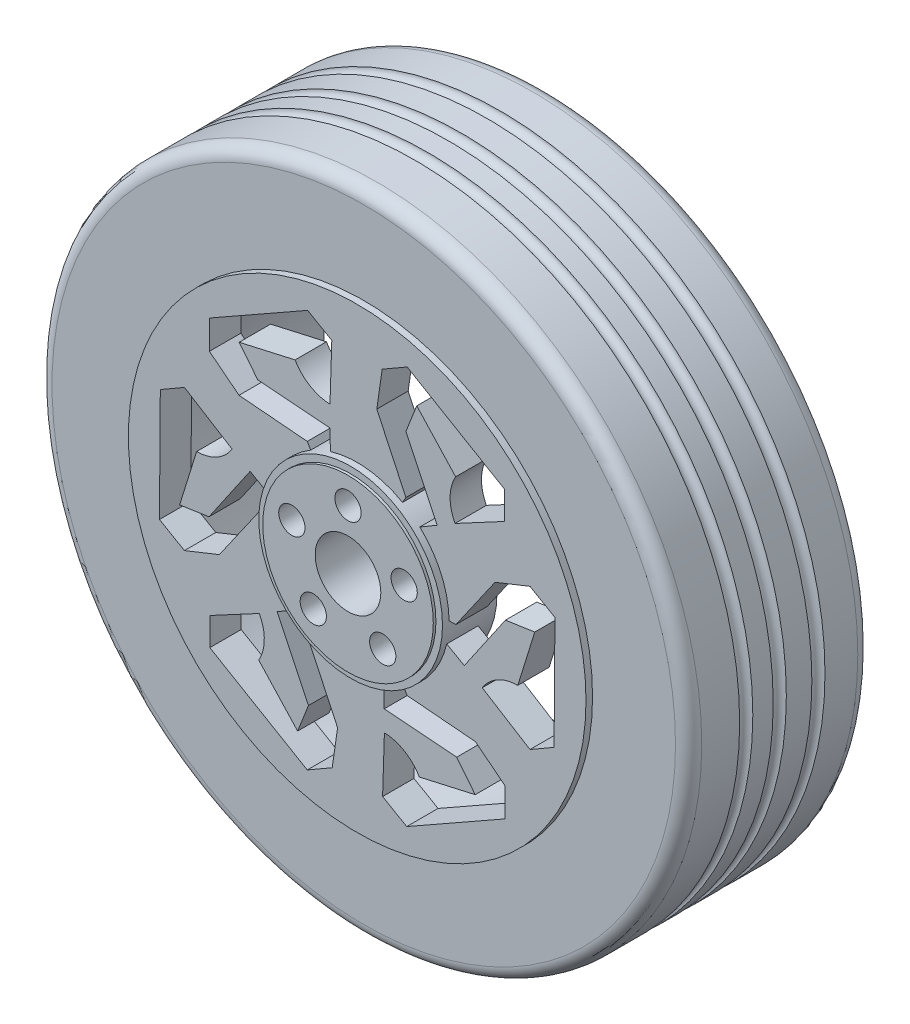
SolidWorks part; units mm, degrees
ref_plane "Front Plane" through (0, 0, 0) normal (0, 0, 1) x (1, 0, 0)
ref_plane "Top Plane" through (0, 0, 0) normal (0, 1, 0) x (1, 0, 0)
ref_plane "Right Plane" through (0, 0, 0) normal (1, 0, 0) x (0, 0, -1)
sketch "Sketch2" plane through (0, 0, 0) normal (0, 0, 1) x (1, 0, 0)
  circle A0 centre (0, 0) radius 247.55
  dimension "D1" = 495.1
extrude "Boss-Extrude1" add sketch "Sketch2" along normal blind 138.9
sketch "Sketch3" plane through (0, 0, 138.9) normal (0, 0, 1) x (1, 0, 0)
  circle A0 centre (0, 0) radius 174.35
  dimension "D1" = 348.7
fillet "Fillet1" radius 10 1 edges at (247.55, 0, 138.9)
fillet "Fillet2" radius 10 1 edges at (247.55, 0, 0)
extrude "Boss-Extrude2" add sketch "Sketch3" along normal blind 5
sketch "Sketch5" plane through (0, 0, 143.9) normal (0, 0, 1) x (1, 0, 0)
  line L0 (105.0037, 43.3694) -> (131.6337, 54.0214)
  line L1 (131.6337, 54.0214) -> (150.6653, 43.0319)
  line L2 (150.6653, 43.0319) -> (150.3446, -0.3609)
  line L3 (150.3446, -0.3609) -> (150.0291, -43.0412)
  line L4 (150.0291, -43.0412) -> (131.6404, -53.6579)
  line L5 (131.6404, -53.6579) -> (95.2902, -31.0843)
  line L7 (122.3632, -15.976) -> (135.2996, 25.6977)
  line L8 (135.2996, 25.6977) -> (112.9256, 22.3447)
  line L10 (112.9256, 22.3447) -> (81.5922, -23.3101)
  line L11 (81.5922, -23.3101) -> (40.2577, 0.1488)
  line L12 (40.2577, 0.1488) -> (75.1777, 0.5509)
  line L13 (75.1777, 0.5509) -> (105.0037, 43.3694)
  line L14 (90.0609, -69.2512) -> (112.6007, -86.9874)
  line L16 (112.6007, -86.9874) -> (112.5994, -108.964)
  line L17 (112.5994, -108.964) -> (74.8597, -130.3827)
  line L18 (74.8597, -130.3827) -> (37.7398, -151.4496)
  line L19 (37.7398, -151.4496) -> (19.3511, -140.8329)
  line L20 (19.3511, -140.8329) -> (20.7253, -98.0659)
  line L21 (47.346, -113.9577) -> (89.9046, -104.3241)
  line L22 (89.9046, -104.3241) -> (75.8138, -86.6241)
  line L23 (19.0329, 141.0088) -> (38.0659, 151.9959)
  line L24 (38.0659, 151.9959) -> (75.4849, 130.0217)
  line L25 (75.4849, 130.0217) -> (112.2893, 108.4084)
  line L26 (112.2893, 108.4084) -> (112.2893, 87.175)
  line L27 (112.2893, 87.175) -> (74.5649, 66.9816)
  line L28 (75.0173, 97.9817) -> (45.395, 130.0217)
  line L29 (45.395, 130.0217) -> (37.1117, 108.9688)
  line L30 (37.1117, 108.9688) -> (60.9833, 59.0059)
  line L31 (60.9833, 59.0059) -> (20, 34.9386)
  line L32 (20, 34.9386) -> (37.1117, 65.3813)
  line L33 (37.1117, 65.3813) -> (14.9428, 112.6206)
  line L34 (14.9428, 112.6206) -> (19.0329, 141.0088)
  line L35 (75.8138, -86.6241) -> (20.6089, -82.316)
  line L36 (20.6089, -82.316) -> (20.2577, -34.7898)
  line L37 (20.2577, -34.7898) -> (38.066, -64.8303)
  line L38 (38.066, -64.8303) -> (90.0609, -69.2512)
  line L39 (-14.9428, -112.6206) -> (-19.0329, -141.0088)
  line L40 (-19.0329, -141.0088) -> (-38.0659, -151.9959)
  line L41 (-38.0659, -151.9959) -> (-75.4849, -130.0217)
  line L42 (-75.4849, -130.0217) -> (-112.2893, -108.4084)
  line L43 (-112.2893, -108.4084) -> (-112.2893, -87.175)
  line L44 (-112.2893, -87.175) -> (-74.5649, -66.9816)
  line L45 (-75.0173, -97.9817) -> (-45.395, -130.0217)
  line L46 (-45.395, -130.0217) -> (-37.1117, -108.9687)
  line L47 (-37.1117, -108.9687) -> (-60.9833, -59.0059)
  line L48 (-60.9833, -59.0059) -> (-20, -34.9386)
  line L49 (-20, -34.9386) -> (-37.1117, -65.3812)
  line L50 (-37.1117, -65.3812) -> (-14.9428, -112.6206)
  line L51 (-105.0037, -43.3694) -> (-131.6337, -54.0214)
  line L52 (-131.6337, -54.0214) -> (-150.6653, -43.0319)
  line L53 (-150.6653, -43.0319) -> (-150.3446, 0.3609)
  line L54 (-150.3446, 0.3609) -> (-150.0291, 43.0412)
  line L55 (-150.0291, 43.0412) -> (-131.6404, 53.6579)
  line L56 (-131.6404, 53.6579) -> (-95.2902, 31.0843)
  line L57 (-122.3632, 15.976) -> (-135.2996, -25.6977)
  line L58 (-135.2996, -25.6977) -> (-112.9256, -22.3447)
  line L59 (-112.9256, -22.3447) -> (-81.5922, 23.3101)
  line L60 (-81.5922, 23.3101) -> (-40.2577, -0.1488)
  line L61 (-40.2577, -0.1488) -> (-75.1777, -0.5509)
  line L62 (-75.1777, -0.5509) -> (-105.0037, -43.3694)
  line L63 (-90.0609, 69.2512) -> (-112.6007, 86.9874)
  line L64 (-112.6007, 86.9874) -> (-112.5994, 108.964)
  line L65 (-112.5994, 108.964) -> (-74.8597, 130.3827)
  line L66 (-74.8597, 130.3827) -> (-37.7398, 151.4496)
  line L67 (-37.7398, 151.4496) -> (-19.3511, 140.8329)
  line L68 (-19.3511, 140.8329) -> (-20.7253, 98.0659)
  line L69 (-47.346, 113.9577) -> (-89.9046, 104.3241)
  line L70 (-89.9046, 104.3241) -> (-75.8138, 86.6241)
  line L71 (-75.8138, 86.6241) -> (-20.6089, 82.316)
  line L72 (-20.6089, 82.316) -> (-20.2577, 34.7898)
  line L73 (-20.2577, 34.7898) -> (-38.066, 64.8303)
  line L74 (-38.066, 64.8303) -> (-90.0609, 69.2512)
  arc A2 (74.5649, 66.9816) -> (75.0173, 97.9817) centre (102.7589, 82.0735) cw
  arc A3 (95.2902, -31.0843) -> (122.3632, -15.976) centre (122.4571, -47.955) cw
  arc A4 (20.7253, -98.0659) -> (47.346, -113.9577) centre (19.6983, -130.0285) cw
  arc A5 (-74.5649, -66.9816) -> (-75.0173, -97.9817) centre (-102.7589, -82.0735) cw
  arc A6 (-95.2902, 31.0843) -> (-122.3632, 15.976) centre (-122.4571, 47.955) cw
  arc A7 (-20.7253, 98.0659) -> (-47.346, 113.9577) centre (-19.6983, 130.0285) cw
  point P87 (0, 0)
  dimension "D1" = 6
sketch "Sketch6" plane through (0, 0, 143.9) normal (0, 0, 1) x (1, 0, 0)
sketch "Sketch8" plane through (0, 0, 143.9) normal (0, 0, 1) x (1, 0, 0)
extrude "Cut-Extrude1" cut sketch "Sketch5" against normal blind 30
sketch "Sketch9" plane through (0, 0, 143.9) normal (0, 0, 1) x (1, 0, 0)
  circle A0 centre (0, 0) radius 73.3512
sketch3d "3DSketch1" plane through (0, 0, 0) normal (0, 0, 1) x (1, 0, 0)
sketch3d "3DSketch2" plane through (0, 0, 0) normal (0, 0, 1) x (1, 0, 0)
sketch "Sketch14" plane through (0, 0, 95) normal (0, 0, 1) x (1, 0, 0)
  circle A0 centre (0, 0) radius 247.55
sketch "Sketch15" plane through (0, 0, 69.45) normal (0, 0, 1) x (1, 0, 0)
  circle A0 centre (0, 0) radius 247.55
sketch "Sketch16" plane through (0, 0, 40) normal (0, 0, 1) x (1, 0, 0)
  circle A0 centre (0, 0) radius 247.55
sketch3d "3DSketch3" plane through (0, 0, 0) normal (0, 0, 1) x (1, 0, 0)
sweep "Cut-Sweep1" cut path "Sketch16" circular profile diameter 10 parameters "D3"=10
sweep "Cut-Sweep2" cut path "Sketch15" circular profile diameter 10 parameters "D3"=10
sweep "Cut-Sweep3" cut path "Sketch14" circular profile diameter 10 parameters "D3"=10
sketch3d "3DSketch4"
  circle A0 centre (0, 0, 0) radius 25
  point P2 (0, 0, 25)
  dimension "D1" = 50
extrude "Cut-Extrude2" cut sketch "3DSketch4" along direction (0, 0, 1) on the side of the normal blind 179
sketch "Sketch22" plane through (0, 0, 0) normal (0, 0, -1) x (-1, 0, 0)
  circle A0 centre (0, 0) radius 140.4764
  dimension "D1" = 280.9527
sketch "Sketch23" plane through (0, 0, 0) normal (0, 0, -1) x (-1, 0, 0)
  circle A0 centre (0, 0) radius 169.35
  dimension "D1" = 338.7
extrude "Cut-Extrude4" cut sketch "Sketch23" against normal blind 120
sketch3d "3DSketch5" plane through (0, 0, 0) normal (0, 0, 1) x (1, 0, 0)
sketch3d "3DSketch6" plane through (0, 0, 0) normal (0, 0, 1) x (1, 0, 0)
  dimension "D1" = 10
sketch "Sketch105" plane through (0, 0, 120) normal (0, 0, -1) x (-1, 0, 0)
  circle A0 centre (0, 0) radius 72.1629
  circle A1 centre (0, 0) radius 25
sketch "Sketch113" plane through (0, 0, 143.9) normal (0, 0, 1) x (1, 0, 0)
  circle A0 centre (0, 0) radius 70
  dimension "D1" = 140
extrude "Boss-Extrude6" add sketch "Sketch113" against normal blind 36.503 and the other way blind 5
sketch "Sketch114" plane through (0, 0, 148.9) normal (0, 0, 1) x (1, 0, 0)
  circle A0 centre (0, 0) radius 65
  dimension "D1" = 130
extrude "Boss-Extrude7" add sketch "Sketch114" along normal blind 2
sketch "Sketch115" plane through (0, 0, 150.9) normal (0, 0, 1) x (1, 0, 0)
  line L0 (0, 25) -> (0, 65) construction
  circle A0 centre (0, 0) radius 25
  circle A1 centre (0, 0) radius 65 construction
  dimension "D1" = 50
extrude "Cut-Extrude6" cut sketch "Sketch115" against normal blind 61
sketch "Sketch116" plane through (0, 0, 150.9) normal (0, 0, 1) x (1, 0, 0)
  line L0 (0, 65) -> (0, 25) construction
  circle A0 centre (0, 0) radius 65 construction
  circle A1 centre (0, 0) radius 25 construction
  circle A2 centre (0, 45) radius 10
  circle A3 centre (42.7975, 13.9058) radius 10
  circle A4 centre (26.4503, -36.4058) radius 10
  circle A5 centre (-26.4503, -36.4058) radius 10
  circle A6 centre (-42.7975, 13.9058) radius 10
  point P20 (0, 0)
  dimension "D1" = 20
  dimension "D2" = 5
extrude "Cut-Extrude7" cut sketch "Sketch116" against normal blind 20
sketch "Sketch117" plane through (0, 0, 130.9) normal (0, 0, 1) x (1, 0, 0)
  line L0 (0, 25) -> (0, 65) construction
  circle A0 centre (0, 0) radius 25 construction
  circle A1 centre (0, 0) radius 65 construction
  circle A2 centre (0, 45) radius 5
  circle A3 centre (42.7975, 13.9058) radius 5
  circle A4 centre (26.4503, -36.4058) radius 5
  circle A5 centre (-26.4503, -36.4058) radius 5
  circle A6 centre (-42.7975, 13.9058) radius 5
  point P20 (0, 0)
  dimension "D1" = 10
  dimension "D2" = 5
extrude "Cut-Extrude8" cut sketch "Sketch117" against normal blind 30
